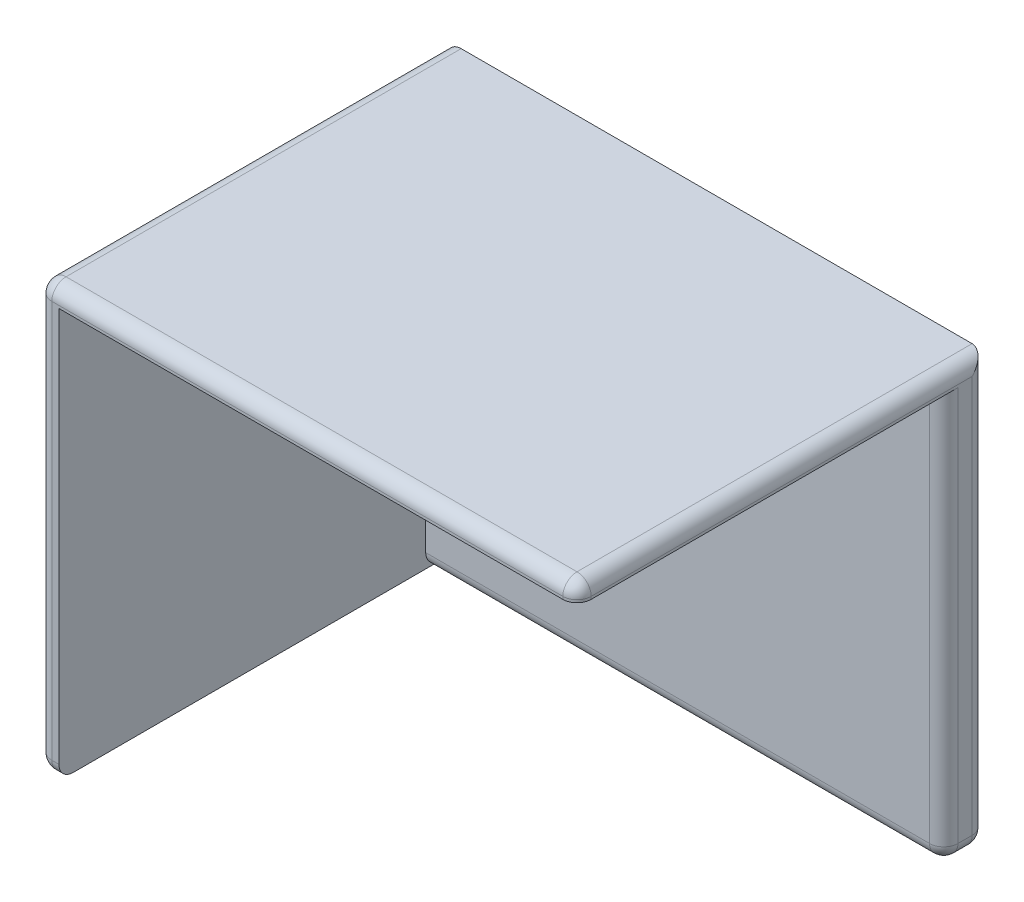
SolidWorks part; units mm, degrees
ref_plane "Front Plane" through (0, 0, 0) normal (0, 0, 1) x (1, 0, 0)
ref_plane "Top Plane" through (0, 0, 0) normal (0, 1, 0) x (1, 0, 0)
ref_plane "Right Plane" through (0, 0, 0) normal (1, 0, 0) x (0, 0, -1)
sketch "Sketch1" plane through (0, 0, 0) normal (0, 0, 1) x (1, 0, 0)
  line L1 (19, -15) -> (-19, -15)
  line L2 (19, -15) -> (19, 15)
  line L3 (19, 15) -> (-19, 15)
  line L4 (-19, -15) -> (-19, 15)
  line L5 (19, -15) -> (-19, 15) construction
  line L6 (19, 15) -> (-19, -15) construction
  line L7 (17.5, -13.8158) -> (-17.5, -13.8158)
  line L8 (17.5, -13.8158) -> (17.5, 13.8158)
  line L9 (17.5, 13.8158) -> (-17.5, 13.8158)
  line L10 (-17.5, -13.8158) -> (-17.5, 13.8158)
  line L11 (17.5, -13.8158) -> (-17.5, 13.8158) construction
  line L12 (17.5, 13.8158) -> (-17.5, -13.8158) construction
  point P0 (0, 0)
  point P6 (0, 0)
  dimension "D1" = 30
  dimension "D2" = 38
  dimension "D3" = 1.5
extrude "Boss-Extrude1" add sketch "Sketch1" along normal blind 28.84
fillet "Fillet1" radius 1 4 edges at (19, 0, 28.84) (0, -15, 28.84) (-19, 0, 28.84) (0, 15, 28.84)
sketch "Sketch2" plane through (0, 0, 0) normal (0, 0, -1) x (-1, 0, 0)
  line L1 (-17.5, 13.8158) -> (17.5, 13.8158)
  line L2 (-17.5, 13.8158) -> (-17.5, -13.8158)
  line L3 (-17.5, -13.8158) -> (17.5, -13.8158)
  line L4 (17.5, 13.8158) -> (17.5, -13.8158)
extrude "Boss-Extrude2" add sketch "Sketch2" against normal blind 3
sketch "Sketch3" plane through (0, 0, 3) normal (0, 0, -1) x (-1, 0, 0)
  line L1 (-19, -15) -> (17.5, -15)
  line L2 (-19, -15) -> (-19, 13.8158)
  line L3 (-19, 13.8158) -> (17.5, 13.8158)
  line L4 (17.5, -15) -> (17.5, 13.8158)
extrude "Cut-Extrude1" cut sketch "Sketch3" against normal through all
fillet "Fillet2" radius 1 11 edges at (18.7071, 14.7071, 28.5471) (-18.7071, -14.7071, 28.5471) (-18.7071, 14.7071, 28.5471) (0.75, -15, 3) (19, -0.5921, 3) (19, 0, 0) (0, -15, 0) (19, -15, 1.5) (19, 15, 13.92) (-19, -15, 13.92) (-19, 15, 13.92)
